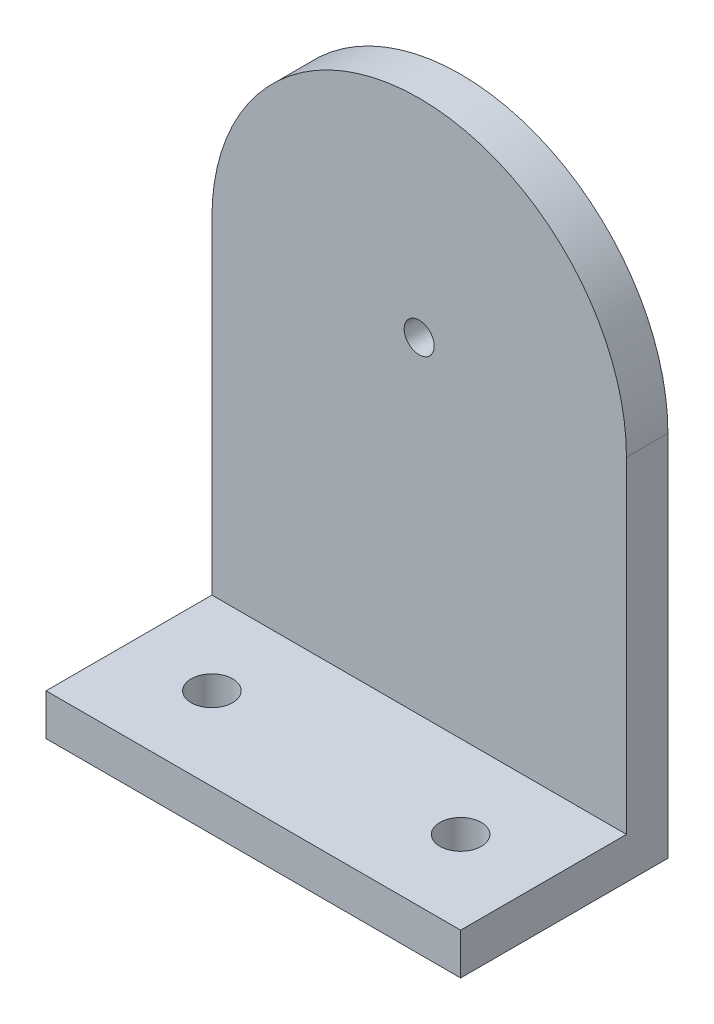
SolidWorks part; units mm, degrees
ref_plane "Front Plane" through (0, 0, 0) normal (0, 0, 1) x (1, 0, 0)
ref_plane "Top Plane" through (0, 0, 0) normal (0, 1, 0) x (1, 0, 0)
ref_plane "Right Plane" through (0, 0, 0) normal (1, 0, 0) x (0, 0, -1)
sketch "Sketch1" plane through (0, 0, 0) normal (0, 0, 1) x (1, 0, 0)
  line L1 (-15.875, 0) -> (15.875, 0)
  line L2 (-15.875, 0) -> (-15.875, -28.194)
  line L3 (-15.875, -28.194) -> (15.875, -28.194)
  line L4 (15.875, 0) -> (15.875, -28.194)
  circle A0 centre (0, 0) radius 15.875
  arc A2 (-15.875, 0) -> (15.875, 0) centre (0, 0) ccw
  dimension "D1" = 31.75
  dimension "D2" = 28.194
extrude "Boss-Extrude1" add sketch "Sketch1" along normal blind 3.175 contours A0 | L2 L1 L4 L3
sketch "Sketch4" plane through (0, 0, 3.175) normal (0, 0, 1) x (1, 0, 0)
  line L0 (15.875, 0) -> (15.875, -28.194) construction
  line L1 (-15.875, -28.194) -> (15.875, -28.194)
  line L2 (-15.875, -28.194) -> (-15.875, -25.019)
  line L3 (-15.875, -25.019) -> (15.875, -25.019)
  line L4 (15.875, -28.194) -> (15.875, -25.019)
  dimension "D1" = 3.175
extrude "Boss-Extrude2" add sketch "Sketch4" along normal blind 12.7
sketch "Sketch5" plane through (0, -25.019, 0) normal (0, 1, 0) x (1, 0, 0)
  line L0 (-15.875, -9.525) -> (15.875, -9.525) construction
  line L1 (-15.875, -15.875) -> (-15.875, -3.175) construction
  line L2 (15.875, -15.875) -> (15.875, -3.175) construction
  line L3 (0, -3.175) -> (0, -15.875) construction
  line L4 (15.875, -3.175) -> (-15.875, -3.175) construction
  line L5 (15.875, -15.875) -> (-15.875, -15.875) construction
  circle A0 centre (-9.525, -9.525) radius 1.5875
  circle A1 centre (9.525, -9.525) radius 1.5875
  dimension "D1" = 3.175
  dimension "D2" = 9.525
extrude "Cut-Extrude2" cut sketch "Sketch5" against normal through all
sketch "Sketch6" plane through (0, 0, 3.175) normal (0, 0, 1) x (1, 0, 0)
  circle A0 centre (0, 0) radius 1.15
  dimension "D1" = 2.3
extrude "Cut-Extrude3" cut sketch "Sketch6" against normal through all
